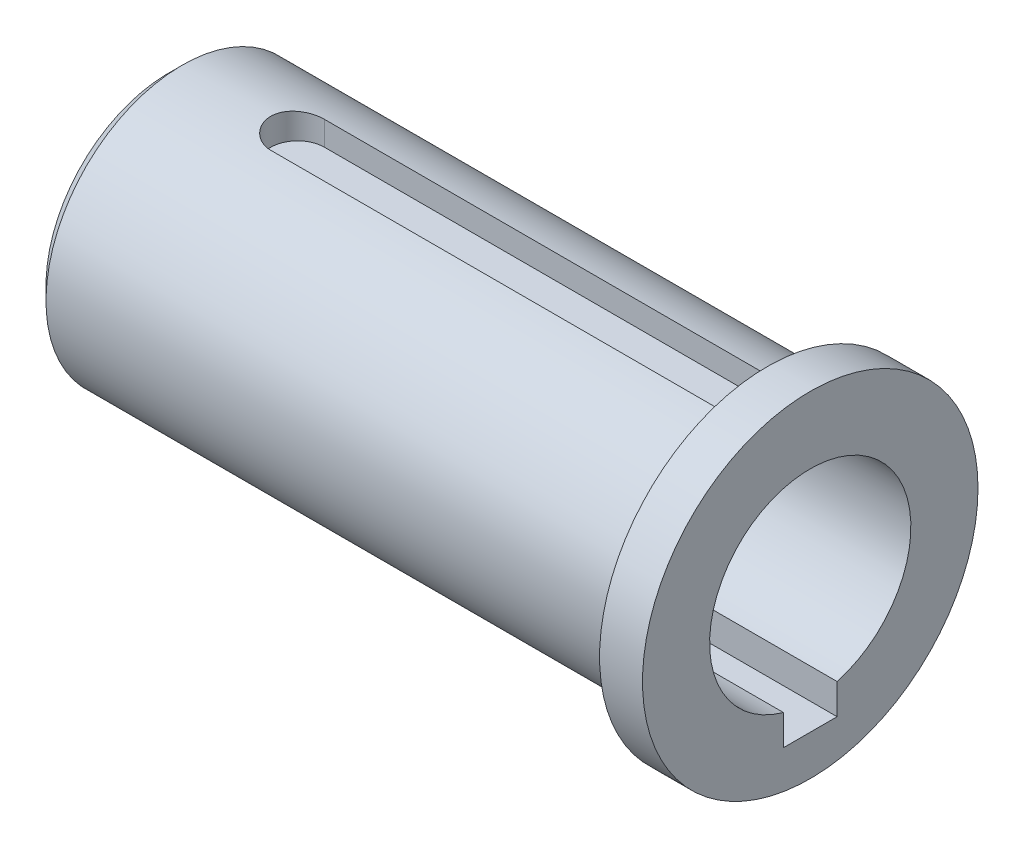
SolidWorks part; units mm, degrees
ref_plane "Front Plane" through (0, 0, 0) normal (0, 0, 1) x (1, 0, 0)
ref_plane "Top Plane" through (0, 0, 0) normal (0, 1, 0) x (1, 0, 0)
ref_plane "Right Plane" through (0, 0, 0) normal (1, 0, 0) x (0, 0, -1)
sketch "Sketch1" plane through (0, 0, 0) normal (1, 0, 0) x (0, 0, -1)
  circle A0 centre (0, 0) radius 10.15
  circle A1 centre (0, 0) radius 7.5
  dimension "D1" = 20.3
  dimension "D2" = 15
extrude "Boss-Extrude1" add sketch "Sketch1" along normal blind 47.8
sketch "Sketch2" plane through (47.8, 0, 0) normal (1, 0, 0) x (0, 0, -1)
  circle A0 centre (0, 0) radius 12.5
  circle A1 centre (0, 0) radius 10.15 construction
  circle A2 centre (0, 0) radius 10.15
  dimension "D1" = 25
extrude "Boss-Extrude2" add sketch "Sketch2" against normal blind 3.2
sketch "Sketch5" plane through (0, 0, 0) normal (-1, 0, 0) x (0, 0, 1)
  line L0 (-2, -9.5) -> (-2, -5.5)
  line L1 (-2, -9.5) -> (2, -9.5)
  line L2 (-2, -5.5) -> (2, -5.5)
  line L3 (2, -9.5) -> (2, -5.5)
  line L4 (-2, -9.5) -> (2, -5.5) construction
  line L5 (-2, -5.5) -> (2, -9.5) construction
  line L6 (0, 0) -> (0, -7.5) construction
  circle A0 centre (0, 0) radius 7.5 construction
  point P1 (0, -7.5)
  dimension "D1" = 4
extrude "Cut-Extrude2" cut sketch "Sketch5" against normal through all
sketch "Sketch6" plane through (0, 0, 0) normal (-1, 0, 0) x (0, 0, 1)
  line L0 (-2, 12.15) -> (-2, 8.15)
  line L1 (-2, 12.15) -> (2, 12.15)
  line L2 (-2, 8.15) -> (2, 8.15)
  line L3 (2, 12.15) -> (2, 8.15)
  line L4 (-2, 12.15) -> (2, 8.15) construction
  line L5 (-2, 8.15) -> (2, 12.15) construction
  line L6 (-2, -9.5) -> (2, -9.5) construction
  line L7 (0, 0) -> (0, 10.15) construction
  circle A0 centre (0, 0) radius 10.15 construction
  point P1 (0, 10.15)
extrude "Cut-Extrude3" cut sketch "Sketch6" against normal blind 20 from offset 10 offset against normal yes
sketch "Sketch4" plane through (0, 0, 0) normal (0, 1, 0) x (1, 0, 0)
  line L0 (9.6, 0) -> (42.6, 0) construction
  line L1 (9.6, 2) -> (42.6, 2)
  line L2 (9.6, -2) -> (42.6, -2)
  line L3 (44.6, 12.5) -> (44.6, -12.5) construction
  arc A0 (9.6, 2) -> (9.6, -2) centre (9.6, 0) ccw
  arc A1 (42.6, -2) -> (42.6, 2) centre (42.6, 0) ccw
  point P2 (26.1, 0)
  dimension "D1" = 33
  dimension "D2" = 4
extrude "Cut-Extrude1" cut sketch "Sketch4" along normal blind 10 from vertex starting at point (30, 8.15, -2)
chamfer "Chamfer1" distance 1 angle 45 1 edges at (0, 0, -10.15)
move or copy body "Body-Move/Copy1" [suppressed] bodies to move or copy 103
